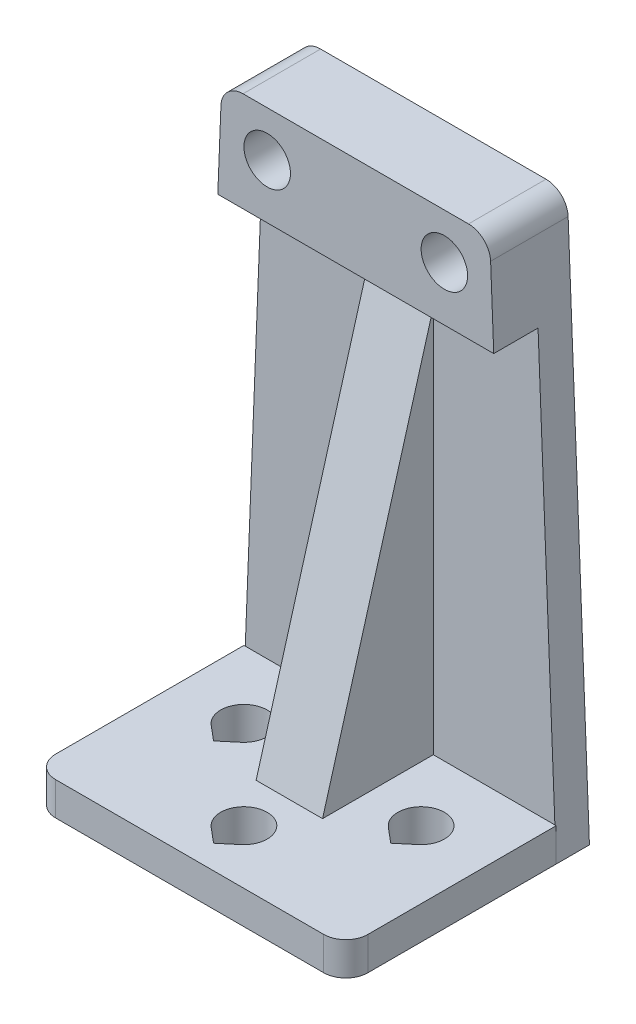
SolidWorks part; units mm, degrees
ref_plane "Front Plane" through (0, 0, 0) normal (0, 0, 1) x (1, 0, 0)
ref_plane "Top Plane" through (0, 0, 0) normal (0, 1, 0) x (1, 0, 0)
ref_plane "Right Plane" through (0, 0, 0) normal (1, 0, 0) x (0, 0, -1)
sketch "Sketch1" plane through (0, 0, 0) normal (0, 1, 0) x (1, 0, 0)
  line L0 (-8, -6.1) -> (8, -6.1) construction
  line L1 (-14.1, -19) -> (14.1, -19)
  line L2 (-14.1, -19) -> (-14.1, 0)
  line L3 (-14.1, 0) -> (14.1, 0)
  line L4 (14.1, -19) -> (14.1, 0)
  line L5 (-9.3499, -7.7087) -> (-8, -8.8414)
  line L6 (-8, -8.8414) -> (-6.6501, -7.7087)
  line L7 (-1.3499, -15.7087) -> (0, -16.8414)
  line L8 (0, -16.8414) -> (1.3499, -15.7087)
  line L9 (6.6501, -7.7087) -> (8, -8.8414)
  line L10 (8, -8.8414) -> (9.3499, -7.7087)
  arc A0 (-6.6501, -7.7087) -> (-9.3499, -7.7087) centre (-8, -6.1) ccw
  arc A1 (9.3499, -7.7087) -> (6.6501, -7.7087) centre (8, -6.1) ccw
  arc A2 (1.3499, -15.7087) -> (-1.3499, -15.7087) centre (0, -14.1) ccw
  point P4 (0, 0)
  point P10 (0, -6.1)
  dimension "D3" = 4.2
  dimension "D1" = 28.2
  dimension "D2" = 19
  dimension "D4" = 16
  dimension "D5" = 4
  dimension "D6" = 8
  dimension "D7" = 100
  dimension "D8" = 100
  dimension "D9" = 100
extrude "Boss-Extrude1" add sketch "Sketch1" along normal blind 3
sketch "Sketch2" plane through (0, 0, 0) normal (0, 0, -1) x (-1, 0, 0)
  line L0 (-8, 46) -> (8, 46) construction
  line L1 (-14.1, 0) -> (14.1, 0)
  line L2 (-14.1, 0) -> (-12.1, 50.1)
  line L3 (-12.1, 50.1) -> (12.1, 50.1)
  line L4 (14.1, 0) -> (12.1, 50.1)
  circle A0 centre (-8, 46) radius 2.1
  circle A1 centre (8, 46) radius 2.1
  point P5 (0, 46)
  point P12 (0, 50.1)
  dimension "D1" = 4.2
  dimension "D2" = 16
  dimension "D3" = 2
  dimension "D4" = 2
  dimension "D5" = 46
extrude "Boss-Extrude2" add sketch "Sketch2" along normal blind 3
sketch "Sketch3" plane through (0, 0, 0) normal (1, 0, 0) x (0, 0, -1)
  line L0 (0, 3) -> (-10, 3)
  line L1 (-19, 3) -> (0, 3) construction
  line L2 (-10, 3) -> (0, 38)
  line L3 (0, 50.1) -> (0, 3) construction
  line L4 (0, 38) -> (0, 3)
  dimension "D1" = 10
  dimension "D2" = 35
extrude "Boss-Extrude3" add sketch "Sketch3" along normal mid plane 6
fillet "Fillet1" radius 2 4 edges at (12.1, 50.1, -1.5) (-12.1, 50.1, -1.5) (14.1, 1.5, 19) (-14.1, 1.5, 19)
sketch "Sketch4" plane through (0, 0, 0) normal (0, 0, 1) x (1, 0, 0)
  line L0 (-10.1782, 50.1) -> (10.1782, 50.1) construction
  line L1 (-10.1782, 50.1) -> (10.1782, 50.1)
  line L2 (-12.1767, 48.1798) -> (-12.4593, 41.1)
  line L3 (-13.9802, 3) -> (-12.1767, 48.1798) construction
  line L4 (-12.4593, 41.1) -> (12.4593, 41.1)
  line L5 (12.1767, 48.1798) -> (13.9802, 3) construction
  line L6 (12.4593, 41.1) -> (12.1767, 48.1798)
  circle A0 centre (-8, 46) radius 2.1 construction
  circle A1 centre (8, 46) radius 2.1 construction
  arc A2 (12.1767, 48.1798) -> (10.1782, 50.1) centre (10.1782, 48.1) ccw construction
  arc A3 (-10.1782, 50.1) -> (-12.1767, 48.1798) centre (-10.1782, 48.1) ccw construction
  circle A4 centre (-8, 46) radius 2.1
  circle A5 centre (8, 46) radius 2.1
  arc A6 (12.1767, 48.1798) -> (10.1782, 50.1) centre (10.1782, 48.1) ccw
  arc A7 (-10.1782, 50.1) -> (-12.1767, 48.1798) centre (-10.1782, 48.1) ccw
  dimension "D1" = 9
extrude "Boss-Extrude4" add sketch "Sketch4" along normal blind 4
equation "\"width\"= 24"
equation "\"thk\"= 3"
equation "\"holesize\"= 4.2"
equation "\"holedistance\"= ( 20 + 12 ) / 2"
equation "\"threaded_hole\"= 3.9"
equation "\"fillet_radius\"= 2"
equation "\"ground_clearance\"= 25"
equation "\"tire_thk\"= 3"
equation "\"innerwheel_diam\" = \"wheel_diam\"-2*\"tire_thk\""
equation "\"innerwheel_thk\"= 8"
equation "\"wheel_diam\"= 2*(\"width\"/2+\"ground_clearance\")"
equation "\"coloursensor_holesize\"= 2.65"
equation "\"hole_to_edge\" = 4"
equation "\"D1@Sketch1\"=\"holedistance\"+ \"holesize\" + 2 * \"hole_to_edge\""
equation "\"D3@Sketch1\"=\"holesize\""
equation "\"D4@Sketch1\"=\"holedistance\""
equation "\"D6@Sketch1\"=\"holedistance\"/2"
equation "\"D5@Sketch1\"=\"hole_to_edge\""
equation "\"D1@Boss-Extrude1\"=\"thk\""
equation "\"D1@Sketch2\"=\"holesize\""
equation "\"D2@Sketch2\"=\"holedistance\""
equation "\"D4@Sketch2\"=\"D3@Sketch2\""
equation "\"D1@Boss-Extrude2\"=\"thk\""
equation "\"D1@Fillet1\"=\"fillet_radius\""
equation "\"D8@Sketch1\"=\"D7@Sketch1\""
equation "\"D9@Sketch1\"=\"D7@Sketch1\""
equation "\"D5@Sketch2\"=42 + \"thk\" + 1"
